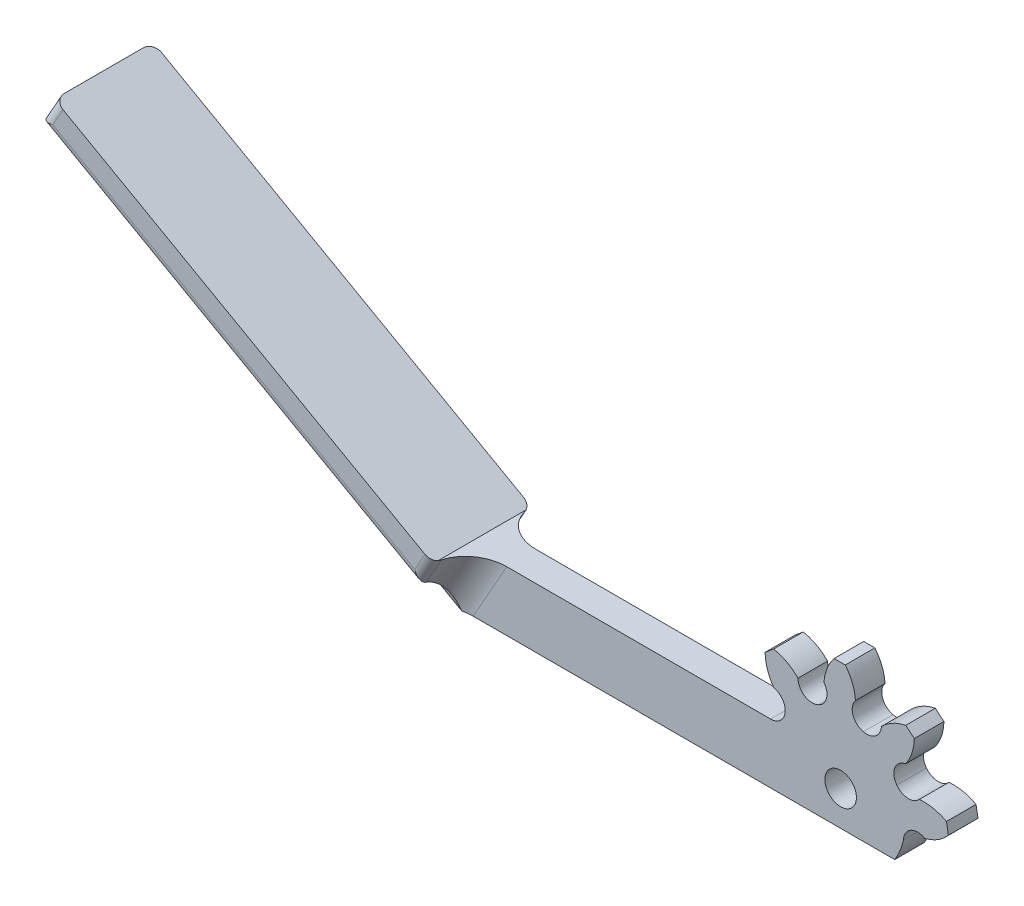
SolidWorks part; units mm, degrees
material "PLA"
ref_plane "Front Plane" through (0, 0, 0) normal (0, 0, 1) x (1, 0, 0)
ref_plane "Top Plane" through (0, 0, 0) normal (0, 1, 0) x (1, 0, 0)
ref_plane "Right Plane" through (0, 0, 0) normal (1, 0, 0) x (0, 0, -1)
other "Graphic1"
other "Graphic (Closed) -1"
sketch "Sketch1" plane through (0, 0, 0) normal (0, 0, 1) x (1, 0, 0)
  line L9 (58.4169, 4.9748) -> (58.2202, 6.0904)
  line L15 (40.7071, 12.4718) -> (39.8394, 11.7436)
  line L16 (47.9681, 14.6994) -> (46.8353, 14.6994)
  line L17 (54.9622, 11.7386) -> (54.0944, 12.4668)
  line L18 (36.5768, 6.098) -> (36.3801, 4.9825) [skipped]
  line L20 (37.5098, -1.4394) -> (38.0761, -2.4205) [skipped]
  line L21 (43.0694, -6.6138) -> (44.1339, -7.0012) [skipped]
  line L22 (50.6544, -7.0039) -> (51.7189, -6.6165) [skipped]
  line L23 (56.7156, -2.4272) -> (57.282, -1.4462) [skipped]
  line L25 (52.9772, 0.125) -> (8.1221, 0.125)
  line L26 (40.4049, 6.1715) -> (9.6549, 6.1715)
  line L27 (9.6549, 6.1715) -> (-28.6718, 27.7851)
  line L28 (8.1221, 0.125) -> (-31.6287, 22.5417)
  line L29 (-31.6287, 22.5417) -> (-28.6718, 27.7851)
  circle A2 centre (47.5, 3.625) radius 1.6
  arc A4 (56.0302, 3.5041) -> (53.8707, 2.3118) centre (55.308, 2.2604) ccw
  arc A5 (56.0302, 3.5041) -> (58.4169, 4.9748) centre (54.9085, 7.9964) ccw
  arc A6 (52.9772, 0.125) -> (53.8707, 2.3118) centre (47.2775, 3.7298) ccw
  arc A7 (58.2202, 6.0904) -> (55.4744, 6.6561) centre (55.9197, 1.8711) ccw
  arc A8 (55.4744, 6.6561) -> (53.1914, 6.7765) centre (54.3818, 7.6424) cw
  arc A29 (40.7223, 9.0829) -> (40.4049, 6.1715) centre (40.4145, 7.6435) cw
  arc A30 (39.8394, 11.7436) -> (40.7223, 9.0829) centre (44.6436, 11.8611) ccw
  arc A31 (43.1741, 11.1402) -> (40.7071, 12.4718) centre (39.8445, 7.9227) ccw
  arc A32 (43.1741, 11.1402) -> (45.2864, 9.8662) centre (44.6123, 11.1367) ccw
  arc A33 (45.8014, 12.0936) -> (45.2864, 9.8662) centre (44.6404, 11.1888) cw
  arc A34 (46.8353, 14.6994) -> (45.8014, 12.0936) centre (50.591, 11.7013) ccw
  arc A35 (49.002, 12.0936) -> (47.9681, 14.6994) centre (44.3832, 11.7691) ccw
  arc A36 (49.002, 12.0936) -> (49.8012, 9.7599) centre (50.1014, 11.1665) ccw
  arc A37 (51.6275, 11.1352) -> (49.8012, 9.7599) centre (50.1565, 11.1884) cw
  arc A38 (54.0944, 12.4668) -> (51.6275, 11.1352) centre (55.0443, 7.756) ccw
  arc A39 (54.0792, 9.0779) -> (54.9622, 11.7386) centre (50.3324, 11.7982) ccw
  arc A40 (54.0792, 9.0779) -> (53.1914, 6.7765) centre (54.3255, 7.6609) ccw
  arc A41 (36.3801, 4.9825) -> (38.7668, 3.5118) centre (39.9849, 8.1605) ccw [skipped]
  arc A42 (39.3225, 6.6637) -> (38.1205, 6.6327) centre (38.8401, 2.0588) ccw [skipped]
  arc A43 (38.3525, 1.2373) -> (40.9094, 2.4457) centre (39.4562, 2.2113) cw [skipped]
  arc A44 (39.2495, 0.7588) -> (40.8709, 2.6178) centre (39.5027, 2.1746) ccw [skipped]
  arc A45 (38.4387, 0.0628) -> (37.5098, -1.4394) centre (41.84, -3.0789) ccw [skipped]
  arc A46 (38.0761, -2.4205) -> (40.8498, -2.0129) centre (38.7948, 2.3311) ccw [skipped]
  arc A47 (40.8498, -2.0129) -> (43.0363, -1.3453) centre (42.2139, -2.5661) cw [skipped]
  arc A48 (42.9891, -3.8116) -> (43.0363, -1.3453) centre (42.2731, -2.5643) ccw [skipped]
  arc A49 (42.9891, -3.8116) -> (43.0694, -6.6138) centre (47.4404, -5.0863) ccw [skipped]
  arc A50 (44.1339, -7.0012) -> (45.9967, -4.9062) centre (41.6301, -2.8994) ccw [skipped]
  arc A51 (45.9967, -4.9062) -> (47.2425, -2.9893) centre (47.3972, -4.4531) cw [skipped]
  arc A52 (48.7916, -4.9089) -> (50.6544, -7.0039) centre (53.0209, -3.0242) ccw [skipped]
  arc A53 (48.7916, -4.9089) -> (47.2425, -2.9893) centre (47.4414, -4.4137) ccw [skipped]
  arc A54 (51.7189, -6.6165) -> (51.7992, -3.8142) centre (47.1642, -5.0837) ccw [skipped]
  arc A55 (51.7992, -3.8142) -> (51.5213, -1.545) centre (52.5808, -2.5669) cw [skipped]
  arc A56 (53.942, -2.0197) -> (51.5213, -1.545) centre (52.5893, -2.5083) ccw [skipped]
  arc A57 (53.942, -2.0197) -> (56.7156, -2.4272) centre (55.9703, 2.1426) ccw [skipped]
  arc A58 (57.282, -1.4462) -> (55.5422, 0.7521) centre (52.8077, -3.1996) ccw [skipped]
  arc A59 (55.5422, 0.7521) -> (53.8707, 2.3118) centre (55.3392, 2.21) cw [skipped]
  arc A60 (39.3225, 6.6637) -> (39.3492, 6.6327) centre (40.4265, 7.5855) ccw [skipped]
  point P120 (47.3978, 3.6109)
  dimension "D1" = 39.3779
  dimension "D2" = 37.8451
  dimension "D4" = 150.58
  dimension "D5" = 45.636
  dimension "D3" = 9
extrude "Boss-Extrude1" add sketch "Sketch1" along normal blind 3
sketch "Sketch3" plane through (0, 0, 0) normal (0, 0, -1) x (-1, 0, 0)
  line L1 (-53.65, 5.025) -> (-50.35, 5.025)
  line L2 (-53.65, 5.025) -> (-53.65, 2.225)
  line L3 (-53.65, 2.225) -> (-50.35, 2.225)
  line L4 (-50.35, 5.025) -> (-50.35, 2.225)
  line L5 (-44.65, 5.025) -> (-41.35, 5.025)
  line L6 (-44.65, 5.025) -> (-44.65, 2.225)
  line L7 (-44.65, 2.225) -> (-41.35, 2.225)
  line L8 (-41.35, 5.025) -> (-41.35, 2.225)
  circle A0 centre (-47.5, 3.625) radius 1.6
extrude "Cut-Extrude3" cut sketch "Sketch3" against normal blind 2.5 contours L6 L5 L8 L7 | L2 L1 L4 L3 | A0
sketch "Sketch4" plane through (-33.642, 18.9717, 0) normal (-0.871, 0.4912, 0) x (0, 0, 1)
  line L0 (-3.5, 10.1182) -> (6.5, 10.1182)
  line L1 (6.5, 10.1182) -> (6.5, 7.1182)
  line L2 (6.5, 7.1182) -> (-3.5, 7.1182)
  line L3 (-3.5, 7.1182) -> (-3.5, 10.1182)
  line L4 (0, 10.1182) -> (0, 4.0985) construction
  line L5 (3, 10.1182) -> (3, 4.0985) construction
  dimension "D1" = 3.5
  dimension "D2" = 3.5
  dimension "D3" = 3
extrude "Boss-Extrude2" add sketch "Sketch4" against normal up to vertex (44.0009 mm away)
fillet "Fillet1" radius 3.5 2 edges at (-10.9821, 14.3652, 3) (-10.9821, 14.3652, 0)
fillet "Fillet2" radius 3.5 2 edges at (8.1764, 3.5498, 3) (8.1764, 3.5498, 0)
fillet "Fillet3" radius 1 10 edges at (-31.6287, 22.5417, 1.5) (-11.7533, 11.3334, 3) (8.1221, 0.125, 1.5) (-11.7533, 11.3334, 0) (-29.4086, 26.4786, 6.5) (-10.9821, 14.3652, 6.5) (8.918, 4.865, 6.5) (8.918, 4.865, -3.5) (-29.4086, 26.4786, -3.5) (-10.9821, 14.3652, -3.5)
